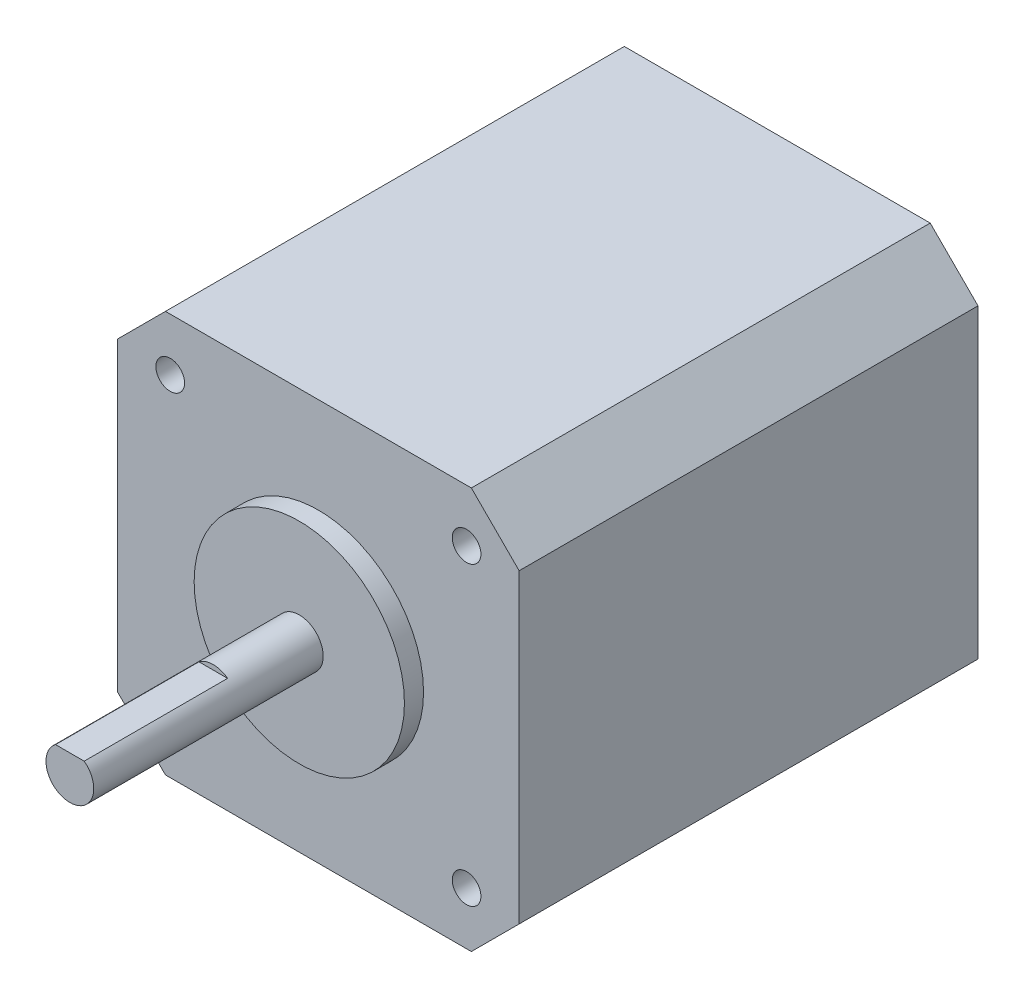
SolidWorks part; units mm, degrees
ref_plane "Front Plane" through (0, 0, 0) normal (0, 0, 1) x (1, 0, 0)
ref_plane "Top Plane" through (0, 0, 0) normal (0, 1, 0) x (1, 0, 0)
ref_plane "Right Plane" through (0, 0, 0) normal (1, 0, 0) x (0, 0, -1)
sketch "Sketch1" plane through (0, 0, 0) normal (0, 0, 1) x (1, 0, 0)
  line L0 (-1.5, 2) -> (1.5, 2)
  line L1 (16, -21) -> (-16, -21)
  line L2 (21, -16) -> (21, 16)
  line L3 (16, 21) -> (-16, 21)
  line L4 (-21, -16) -> (-21, 16)
  line L5 (21, -21) -> (-21, 21) construction
  line L6 (21, 21) -> (-21, -21) construction
  line L7 (15.5, -15.5) -> (-15.5, -15.5) construction
  line L8 (15.5, -15.5) -> (15.5, 15.5) construction
  line L9 (15.5, 15.5) -> (-15.5, 15.5) construction
  line L10 (-15.5, -15.5) -> (-15.5, 15.5) construction
  line L11 (15.5, -15.5) -> (-15.5, 15.5) construction
  line L12 (15.5, 15.5) -> (-15.5, -15.5) construction
  line L13 (0, -2.5) -> (3.3252, -2.5) construction
  line L14 (-16, 21) -> (-21, 16)
  line L15 (21, 16) -> (16, 21)
  line L16 (21, -16) -> (16, -21)
  line L17 (-16, -21) -> (-21, -16)
  circle A0 centre (-15.5, 15.5) radius 1.5
  circle A1 centre (15.5, 15.5) radius 1.5
  circle A2 centre (-15.5, -15.5) radius 1.5
  circle A3 centre (15.5, -15.5) radius 1.5
  circle A4 centre (0, 0) radius 11
  circle A5 centre (0, 0) radius 2.5
  point P0 (0, 0)
  point P6 (0, 0)
  dimension "D5" = 3
  dimension "D6" = 22
  dimension "D7" = 5
  dimension "D1" = 42
  dimension "D2" = 42
  dimension "D3" = 31
  dimension "D4" = 31
  dimension "D8" = 4.5
extrude "Boss-Extrude1" add sketch "Sketch1" against normal blind 48 contours L17 L1 L16 L2 L15 L3 L14 L4 A4 A3 A2 A1 A0 | A4 A5 | L0 A5 | L0 A5 | A2 | A3 | A1 | A0 region at (0, 2.2018, 0) region at (0, -0.1209, 0) region at (0, -20.406, 0) region at (-15.5, 15.5, 0) region at (15.5, 15.5, 0) region at (-15.5, -15.5, 0) region at (15.5, -15.5, 0) region at (-10.6889, 0, 0)
extrude "Boss-Extrude2" add sketch "Sketch1<3>" along normal blind 2 contours A4 A5 region at (-10.6889, 0, 0)
sketch "Sketch1<3>" plane through (0, 0, 0) normal (0, 0, 1) x (1, 0, 0) same geometry as "Sketch1"
extrude "Boss-Extrude3" add sketch "Sketch1<4>" along normal blind 26 contours L0 A5 region at (0, -0.1209, 0)
sketch "Sketch1<4>" plane through (0, 0, 0) normal (0, 0, 1) x (1, 0, 0) same geometry as "Sketch1"
extrude "Boss-Extrude4" add sketch "Sketch1<5>" along normal blind 11 contours L0 A5 region at (0, 2.2018, 0)
sketch "Sketch1<5>" plane through (0, 0, 0) normal (0, 0, 1) x (1, 0, 0) same geometry as "Sketch1"
extrude "Cut-Extrude1" cut sketch "Sketch1<6>" against normal blind 5 contours A0 | A1 | A3 | A2 region at (-15.5, 15.5, 0) region at (15.5, 15.5, 0) region at (-15.5, -15.5, 0) region at (15.5, -15.5, 0)
sketch "Sketch1<6>" plane through (0, 0, 0) normal (0, 0, 1) x (1, 0, 0) same geometry as "Sketch1"
